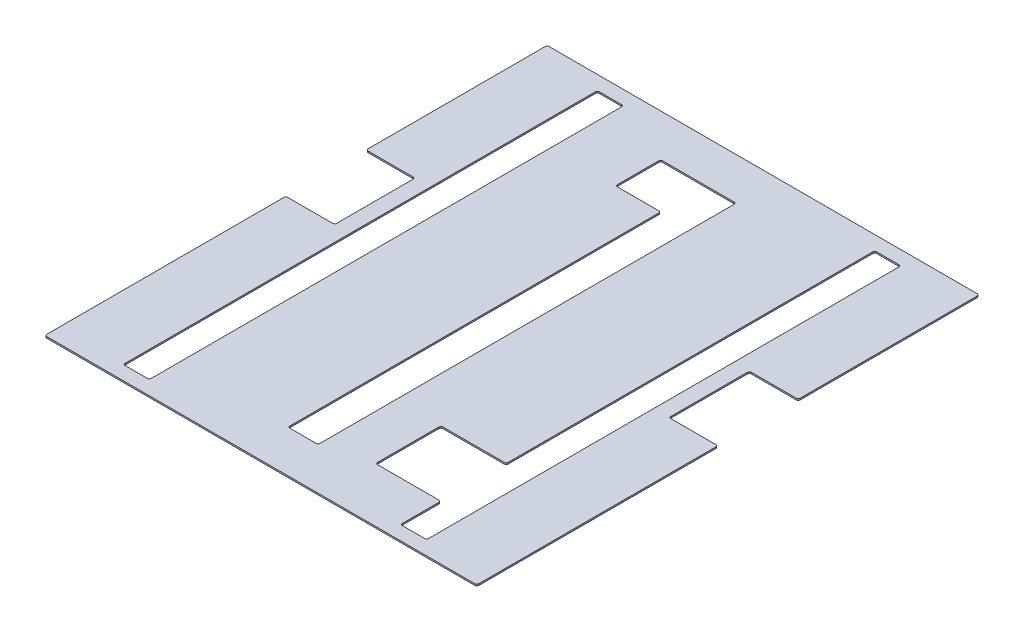
SolidWorks part; units mm, degrees
ref_plane "Front Plane" through (0, 0, 0) normal (0, 0, 1) x (1, 0, 0)
ref_plane "Top Plane" through (0, 0, 0) normal (0, 1, 0) x (1, 0, 0)
ref_plane "Right Plane" through (0, 0, 0) normal (1, 0, 0) x (0, 0, -1)
sketch "Sketch1" plane through (0, 0, 0) normal (0, 1, 0) x (1, 0, 0)
  line L1 (5911.0841, -8452.3124) -> (6341.0841, -8452.3124)
  line L2 (5911.0841, -8452.3124) -> (5911.0841, -8952.3124)
  line L3 (5911.0841, -8952.3124) -> (6341.0841, -8952.3124)
  line L4 (6341.0841, -8452.3124) -> (6341.0841, -8952.3124)
  dimension "D1" = 500
  dimension "D2" = 430
extrude "Boss-Extrude1" add sketch "Sketch1" along normal blind 1.5
sketch "Sketch2" plane through (0, 1.5, 0) normal (0, 1, 0) x (1, 0, 0)
  line L0 (5911.0841, -8452.3124) -> (5911.0841, -8952.3124) construction
  line L1 (5959.6841, -8712.448) -> (5911.0841, -8712.448)
  line L2 (5959.6841, -8712.448) -> (5959.6841, -8632.448)
  line L3 (5959.6841, -8632.448) -> (5911.0841, -8632.448)
  line L4 (5911.0841, -8712.448) -> (5911.0841, -8632.448)
  line L9 (6341.0841, -8952.3124) -> (6341.0841, -8452.3124) construction
  line L10 (6341.0841, -8712.448) -> (6292.4841, -8712.448)
  line L11 (6341.0841, -8712.448) -> (6341.0841, -8632.448)
  line L12 (6341.0841, -8632.448) -> (6292.4841, -8632.448)
  line L13 (6292.4841, -8712.448) -> (6292.4841, -8632.448)
  dimension "D1" = 48.6
  dimension "D2" = 80
  dimension "D3" = 80
  dimension "D4" = 48.6
extrude "Cut-Extrude1" cut sketch "Sketch2" against normal blind 10
sketch "Sketch3" plane through (0, 1.5, 0) normal (0, 1, 0) x (1, 0, 0)
  line L0 (5975.0841, -8541.6519) -> (5975.0841, -8938.3124)
  line L1 (6277.0841, -8938.3124) -> (6251.0841, -8938.3124)
  line L2 (6277.0841, -8938.3124) -> (6277.0841, -8466.3124)
  line L3 (6277.0841, -8466.3124) -> (6251.0841, -8466.3124)
  line L4 (6251.0841, -8938.3124) -> (6251.0841, -8466.3124)
  line L5 (5975.0841, -8466.3124) -> (6001.0841, -8466.3124)
  line L11 (5975.0841, -8938.3124) -> (6001.0841, -8938.3124)
  line L12 (6001.0841, -8466.3124) -> (6001.0841, -8938.3124)
  line L36 (5911.0841, -8712.448) -> (5911.0841, -8952.3124) construction
  line L37 (6341.0841, -8952.3124) -> (6341.0841, -8712.448) construction
  line L39 (6111.0841, -8494.3124) -> (6141.0841, -8494.3124)
  line L40 (6111.0841, -8539.3124) -> (6111.0841, -8910.3124)
  line L41 (6111.0841, -8910.3124) -> (6141.0841, -8910.3124)
  line L42 (6141.0841, -8494.3124) -> (6141.0841, -8910.3124)
  line L44 (6341.0841, -8452.3124) -> (5911.0841, -8452.3124) construction
  line L45 (5975.0841, -8466.3124) -> (5975.0841, -8541.6519)
  line L47 (5911.0841, -8952.3124) -> (6341.0841, -8952.3124) construction
  line L48 (6111.0841, -8494.3124) -> (6066.0841, -8494.3124)
  line L50 (6111.0841, -8539.3124) -> (6066.0841, -8539.3124)
  line L51 (6066.0841, -8494.3124) -> (6066.0841, -8539.3124)
  point P32 (6126.0841, -8452.3124)
  point P33 (6126.0841, -8494.3124)
  dimension "D15" = 42
  dimension "D22" = 45
  dimension "D1" = 26
  dimension "D2" = 472
  dimension "D3" = 26
  dimension "D4" = 472
  dimension "D6" = 64
  dimension "D7" = 45
  dimension "D8" = 64
  dimension "D10" = 416
  dimension "D11" = 110
  dimension "D20" = 14
  dimension "D21" = 14
extrude "Cut-Extrude2" cut sketch "Sketch3" against normal blind 10
sketch "Sketch4" plane through (0, 1.5, 0) normal (0, 1, 0) x (1, 0, 0)
  line L0 (6251.0841, -8466.3124) -> (6251.0841, -8938.3124) construction
  line L1 (6251.0841, -8898.0965) -> (6186.0841, -8898.0965)
  line L2 (6251.0841, -8898.0965) -> (6251.0841, -8833.0965)
  line L3 (6251.0841, -8833.0965) -> (6186.0841, -8833.0965)
  line L4 (6186.0841, -8898.0965) -> (6186.0841, -8833.0965)
  dimension "D1" = 65
  dimension "D2" = 65
extrude "Cut-Extrude3" cut sketch "Sketch4" against normal blind 10
fillet "Fillet2" radius 2 12 edges at (6292.4841, 0.75, 8632.448) (6341.0841, 0.75, 8632.448) (6341.0841, 0.75, 8712.448) (6292.4841, 0.75, 8712.448) (5959.6841, 0.75, 8632.448) (5959.6841, 0.75, 8712.448) (5911.0841, 0.75, 8712.448) (5911.0841, 0.75, 8632.448) (5911.0841, 0.75, 8452.3124) (6341.0841, 0.75, 8452.3124) (6341.0841, 0.75, 8952.3124) (5911.0841, 0.75, 8952.3124)
fillet "Fillet3" radius 2 18 edges at (6001.0841, 0.75, 8938.3124) (5975.0841, 0.75, 8938.3124) (6001.0841, 0.75, 8466.3124) (5975.0841, 0.75, 8466.3124) (6277.0841, 0.75, 8938.3124) (6251.0841, 0.75, 8938.3124) (6277.0841, 0.75, 8466.3124) (6251.0841, 0.75, 8466.3124) (6141.0841, 0.75, 8910.3124) (6111.0841, 0.75, 8910.3124) (6141.0841, 0.75, 8494.3124) (6111.0841, 0.75, 8539.3124) (6066.0841, 0.75, 8494.3124) (6066.0841, 0.75, 8539.3124) (6251.0841, 0.75, 8898.0965) (6251.0841, 0.75, 8833.0965) (6186.0841, 0.75, 8833.0965) (6186.0841, 0.75, 8898.0965)
